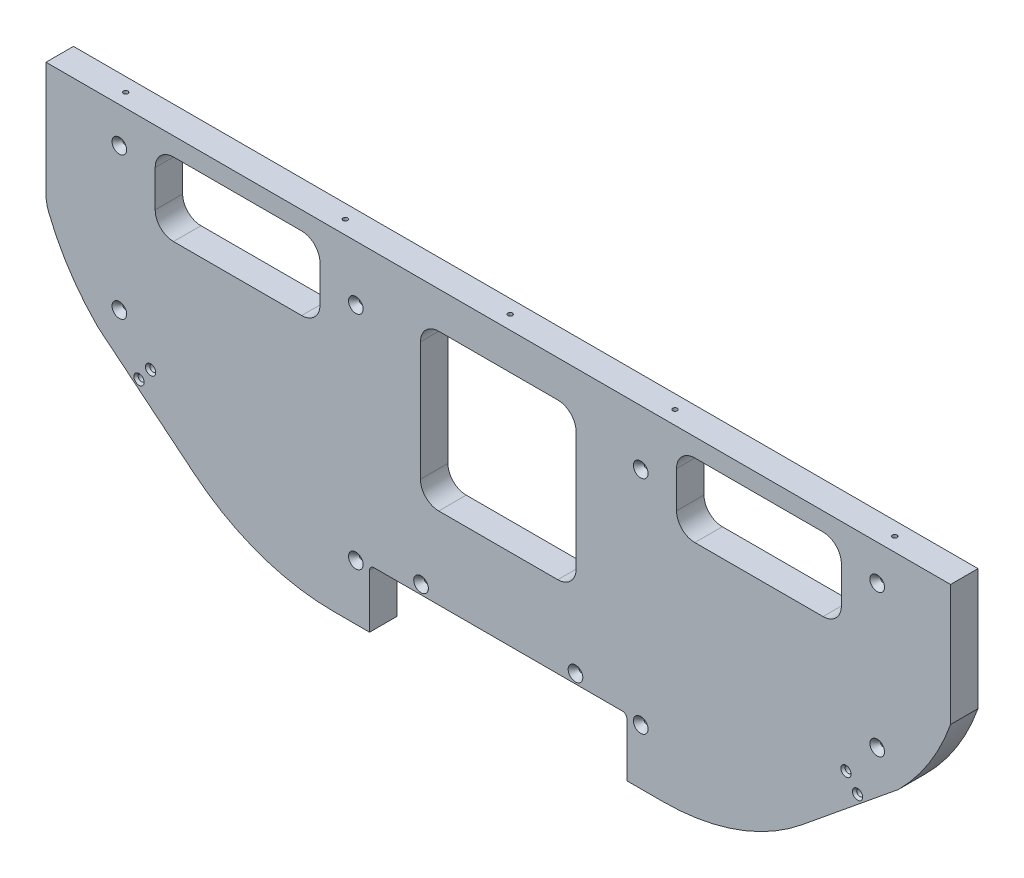
SolidWorks part; units mm, degrees
material "MDF"
ref_plane "Front Plane" through (0, 0, 0) normal (0, 0, 1) x (1, 0, 0)
ref_plane "Top Plane" through (0, 0, 0) normal (0, 1, 0) x (1, 0, 0)
ref_plane "Right Plane" through (0, 0, 0) normal (1, 0, 0) x (0, 0, -1)
sketch "Sketch1" plane through (0, 0, 0) normal (0, 0, 1) x (1, 0, 0)
  line L0 (-394.3667, 18.7383) -> (-394.3667, 23.8125) construction
  line L1 (-1021.7467, -25.3365) -> (-1021.7467, -41.2115) construction
  line L2 (-618.7884, -233.3625) -> (-593.7567, -233.3625) construction
  line L3 (-394.3667, -87.3125) -> (-394.3667, -3.175)
  line L4 (-497.3744, -199.0142) -> (-430.5618, -144.4625)
  line L5 (-709.3267, -233.3625) -> (-593.7567, -233.3625)
  line L6 (-709.3267, -3.175) -> (-709.3267, -233.3625) construction
  line L7 (-1021.7467, -3.175) -> (-396.9067, -3.175) construction
  line L8 (-394.3667, -3.175) -> (-709.3267, -3.175)
  line L9 (-1021.7467, -3.175) -> (-396.9067, -3.175) construction
  line L10 (-976.0267, -152.2395) -> (-918.7391, -199.0142) construction
  line L12 (-985.5517, -144.4625) -> (-918.7391, -199.0142)
  line L13 (-1021.7467, -87.3125) -> (-1021.7467, -3.175)
  line L14 (-822.3567, -233.3625) -> (-709.3267, -233.3625)
  line L15 (-709.3267, -3.175) -> (-1021.7467, -3.175)
  arc A1 (-593.7567, -233.3625) -> (-497.3744, -199.0142) centre (-593.7567, -80.9625) ccw construction
  arc A2 (-430.5618, -144.4625) -> (-394.3667, -87.3125) centre (-538.0037, -36.3792) ccw
  arc A3 (-593.7567, -233.3625) -> (-497.3744, -199.0142) centre (-593.7567, -80.9625) ccw
  arc A4 (-918.7391, -199.0142) -> (-822.3567, -233.3625) centre (-822.3567, -80.9625) ccw construction
  arc A5 (-1021.7467, -87.3125) -> (-985.5517, -144.4625) centre (-878.1098, -36.3792) ccw construction
  arc A6 (-918.7391, -199.0142) -> (-822.3567, -233.3625) centre (-822.3567, -80.9625) ccw
  arc A7 (-1021.7467, -87.3125) -> (-985.5517, -144.4625) centre (-878.1098, -36.3792) ccw
  arc A8 (-430.5618, -144.4625) -> (-394.3668, -87.3125) centre (-538.0037, -36.3792) ccw construction
  point P11 (0, 0)
  point P13 (-709.3267, -3.175)
  point P14 (-394.3668, -84.6839)
  point P28 (0, 0)
  point P29 (0, 0)
  point P30 (0, 0)
  point P31 (0, 0)
  point P32 (0, 0)
  point P37 (0, 0)
extrude "Boss-Extrude1" add sketch "Sketch1" along normal blind 19.05
hole_wizard "5/64 (0.07813) Diameter Hole1" positions "Sketch2" profile "Sketch3" hole size "5/64" standard "ANSI Inch"
sketch "Sketch2" plane through (-708.0567, 15.875, 6128.5599) normal (0, 1, 0) x (1, 0, 0)
  line L1 (-1.27, 6109.5099) -> (-1.27, 6338.7449) construction
  point P0 (-262.8265, 6157.4524)
  point P6 (-98.7933, 6157.4524)
  point P18 (-262.8265, 6233.6524)
  point P19 (-98.7933, 6233.6524)
  point P22 (-262.8265, 6309.8524)
  point P23 (-98.7933, 6309.8524)
  point P24 (-267.97, 6119.0349)
  point P34 (-115.57, 6119.0349)
  point P37 (-1.27, 6119.0349)
  point P40 (113.03, 6119.0349)
  point P44 (265.43, 6119.0349)
  point P55 (98.7933, 6309.8524)
  point P56 (262.8265, 6309.8524)
  point P59 (98.7933, 6233.6524)
  point P60 (262.8265, 6233.6524)
  point P63 (98.7933, 6157.4524)
  point P64 (262.8265, 6157.4524)
  point P111 (0, 0)
  point P112 (0, 0)
  point P113 (0, 0)
  point P114 (0, 0)
sketch "Sketch3" plane through (-970.8832, 15.875, -28.8925) normal (1, 0, 0) x (0, 0, 1)
  line L0 (0, 0) -> (0, 39.0539)
  line L1 (0, 39.0539) -> (1.5875, 38.1)
  line L2 (1.5875, 38.1) -> (1.5875, 4.0177)
  line L3 (1.5875, 4.0177) -> (5.08, 0)
  line L4 (5.08, 0) -> (0, 0)
  line L5 (-1.5875, 4.0177) -> (-5.08, 0) construction
  line L6 (0, 39.0539) -> (-1.5875, 38.1) construction
  line L7 (0, -6.35) -> (0, 107.95) construction
  dimension "Hole Dia." = 3.175
  dimension "Hole Depth" = 38.1
  dimension "Near C'Sink Dia." = 10.16
  dimension "Near C'Sink Angle" = 82
  dimension "Drill Angle" = 118
hole_wizard "5/64 (0.07813) Diameter Hole2" positions "Sketch4" profile "Sketch5" hole size "5/64" standard "ANSI Inch"
sketch "Sketch4" plane through (-708.0567, 1936.854, 19.05) normal (0, 0, 1) x (-1, 0, 0)
  line L23 (262.8265, 2088.1084) -> (262.8265, 2038.7486)
  line L24 (262.8265, 2038.7486) -> (262.8265, 1989.3888)
  line L25 (262.8265, 1989.3888) -> (262.8265, 2038.7486)
  line L26 (262.8265, 2038.7486) -> (262.8265, 1989.3888)
  line L27 (262.8265, 1989.3888) -> (262.8265, 1940.029)
  line L33 (98.7933, 2170.2165) -> (98.7933, 2131.8519)
  line L35 (98.7933, 2131.8519) -> (98.7933, 2093.4873)
  line L36 (98.7933, 2093.4873) -> (98.7933, 2055.1227)
  line L37 (98.7933, 2055.1227) -> (98.7933, 2016.7581)
  line L38 (98.7933, 2016.7581) -> (98.7933, 1978.3935)
  line L39 (98.7933, 1978.3935) -> (98.7933, 1940.029)
  line L44 (89.2683, 2123.544) -> (53.561, 2123.544)
  line L46 (53.561, 2123.544) -> (17.8537, 2123.544)
  line L47 (17.8537, 2123.544) -> (-17.8537, 2123.544)
  line L48 (-17.8537, 2123.544) -> (-53.561, 2123.544)
  line L49 (-53.561, 2123.544) -> (-89.2683, 2123.544)
  line L53 (0, 2170.2165) -> (-0.3175, 1940.029) construction
  line L55 (-99.3221, 1978.6668) -> (-99.4279, 1940.3024)
  line L56 (-99.2163, 2017.0312) -> (-99.3221, 1978.6668)
  line L57 (-99.1104, 2055.3957) -> (-99.2163, 2017.0312)
  line L58 (-99.0046, 2093.7601) -> (-99.1104, 2055.3957)
  line L59 (-98.8988, 2132.1245) -> (-99.0046, 2093.7601)
  line L60 (-98.7929, 2170.489) -> (-98.8988, 2132.1245)
  line L61 (-263.3243, 1990.1145) -> (-263.4605, 1940.7549)
  line L62 (-263.1882, 2039.4741) -> (-263.3243, 1990.1145)
  line L63 (-263.3243, 1990.1145) -> (-263.1882, 2039.4741)
  line L64 (-263.1882, 2039.4741) -> (-263.3243, 1990.1145)
  line L65 (-263.052, 2088.8338) -> (-263.1882, 2039.4741)
  point P71 (262.8265, 1964.7089)
  point P79 (262.8265, 2063.4285)
  point P95 (98.7933, 2131.8519)
  point P103 (98.7933, 1978.3935)
  point P126 (53.561, 2123.544)
  point P134 (-53.561, 2123.544)
  point P162 (-98.7933, 1978.3935)
  point P166 (-98.7933, 2131.8519)
  point P167 (-262.8265, 2063.4285)
  point P169 (-262.8265, 1964.7089)
  point P184 (0, 0)
  point P185 (0, 0)
  point P186 (0, 0)
  point P189 (0, 0)
  point P192 (0, 0)
  point P195 (0, 0)
sketch "Sketch5" plane through (-445.2302, -27.8549, 19.05) normal (1, 0, 0) x (0, -1, 0)
  line L0 (0, 0) -> (0, 39.0539)
  line L1 (0, 39.0539) -> (1.5875, 38.1)
  line L2 (1.5875, 38.1) -> (1.5875, 4.0177)
  line L3 (1.5875, 4.0177) -> (5.08, 0)
  line L4 (5.08, 0) -> (0, 0)
  line L5 (-1.5875, 4.0177) -> (-5.08, 0) construction
  line L6 (0, 39.0539) -> (-1.5875, 38.1) construction
  line L7 (0, -6.35) -> (0, 107.95) construction
  dimension "Hole Dia." = 3.175
  dimension "Hole Depth" = 38.1
  dimension "Near C'Sink Dia." = 10.16
  dimension "Near C'Sink Angle" = 82
  dimension "Drill Angle" = 118
sketch "Sketch6" plane through (0, 0, 0) normal (0, 0, -1) x (-1, 0, 0)
  line L1 (797.325, -233.3625) -> (618.7884, -233.3625)
  line L2 (797.325, -233.3625) -> (797.325, -193.04)
  line L3 (797.325, -193.04) -> (618.7884, -193.04)
  line L4 (618.7884, -233.3625) -> (618.7884, -193.04)
extrude "Cut-Extrude1" cut sketch "Sketch6" against normal up to next
fillet "Fillet1" radius 25.4 2 edges at (-985.5517, -144.4625, 9.525) (-1021.7467, -87.3125, 9.525)
hole_wizard "CSK for #6 Flat Head Machine Screw (100)1" positions "Sketch9" profile "Sketch10" countersink size "#6" standard "ANSI Inch" end condition up to next
sketch "Sketch9" plane through (0, 0, 19.05) normal (0, 0, 1) x (1, 0, 0)
  point P0 (-957.2382, -161.4319)
  point P3 (-949.206, -151.5944)
  point P6 (-466.9052, -151.5924)
  point P9 (-458.8731, -161.4298)
sketch "Sketch10" plane through (-957.2382, -161.4319, 19.05) normal (1, 0, 0) x (0, -1, 0)
  line L0 (0, 0) -> (0, 19.05)
  line L1 (0, 19.05) -> (2.1526, 19.05)
  line L2 (2.1526, 19.05) -> (2.1526, 1.5998)
  line L3 (2.1526, 1.5998) -> (3.5433, 0)
  line L5 (3.5433, 0) -> (0, 0)
  line L6 (-2.1526, 1.5998) -> (-3.5433, 0) construction
  line L11 (0, -6.35) -> (0, 107.95) construction
  dimension "Thru Hole Dia." = 4.3053
  dimension "Thru Hole Depth" = 19.05
  dimension "Near C'Sink Dia." = 7.0866
  dimension "Near C'Sink Angle" = 82
sketch "Sketch12" plane through (0, 0, 19.05) normal (0, 0, 1) x (1, 0, 0)
  line L0 (-708.0567, -193.04) -> (-708.0567, -3.175) construction
  line L1 (-797.325, -193.04) -> (-618.7884, -193.04) construction
  line L2 (-394.3667, -3.175) -> (-1021.7467, -3.175) construction
  line L3 (-970.8832, -27.8549) -> (-806.85, -27.8549) construction
  line L4 (-806.85, -41.5396) -> (-806.85, -27.8549) construction
  line L5 (-584.3968, -15.875) -> (-470.0968, -15.875)
  line L6 (-831.7166, -66.675) -> (-946.0166, -66.675)
  line L7 (-831.7166, -66.675) -> (-831.7166, -15.875)
  line L8 (-831.7166, -15.875) -> (-946.0166, -15.875)
  line L9 (-946.0166, -66.675) -> (-946.0166, -15.875)
  line L10 (-831.7166, -66.675) -> (-946.0166, -15.875) construction
  line L11 (-831.7166, -15.875) -> (-946.0166, -66.675) construction
  line L12 (-470.0968, -66.675) -> (-470.0968, -15.875)
  line L13 (-584.3968, -66.675) -> (-470.0968, -66.675)
  line L14 (-584.3968, -66.675) -> (-584.3968, -15.875)
  line L15 (-394.3667, -3.175) -> (-1021.7467, -3.175) construction
  line L16 (-654.0817, -136.525) -> (-762.0317, -136.525)
  line L17 (-654.0817, -136.525) -> (-654.0817, -28.575)
  line L18 (-654.0817, -28.575) -> (-762.0317, -28.575)
  line L19 (-762.0317, -136.525) -> (-762.0317, -28.575)
  line L20 (-654.0817, -136.525) -> (-762.0317, -28.575) construction
  line L21 (-654.0817, -28.575) -> (-762.0317, -136.525) construction
  point P9 (-888.8666, -27.8549)
  point P10 (-888.8666, -41.275)
  point P20 (-708.0567, -82.55)
  dimension "D1" = 114.3
  dimension "D2" = 50.8
  dimension "D3" = 12.7
  dimension "D4" = 107.95
  dimension "D5" = 107.95
  dimension "D6" = 25.4
extrude "Cut-Extrude2" cut sketch "Sketch12" against normal through all
fillet "Fillet2" radius 12.7 12 edges at (-584.3968, -66.675, 9.525) (-584.3968, -15.875, 9.525) (-470.0968, -15.875, 9.525) (-470.0968, -66.675, 9.525) (-654.0817, -136.525, 9.525) (-654.0817, -28.575, 9.525) (-762.0317, -28.575, 9.525) (-762.0317, -136.525, 9.525) (-946.0166, -66.675, 9.525) (-946.0166, -15.875, 9.525) (-831.7166, -15.875, 9.525) (-831.7166, -66.675, 9.525)
fillet "Fillet3" radius 3.175 2 edges at (-618.7884, -193.04, 9.525) (-797.325, -193.04, 9.525)
